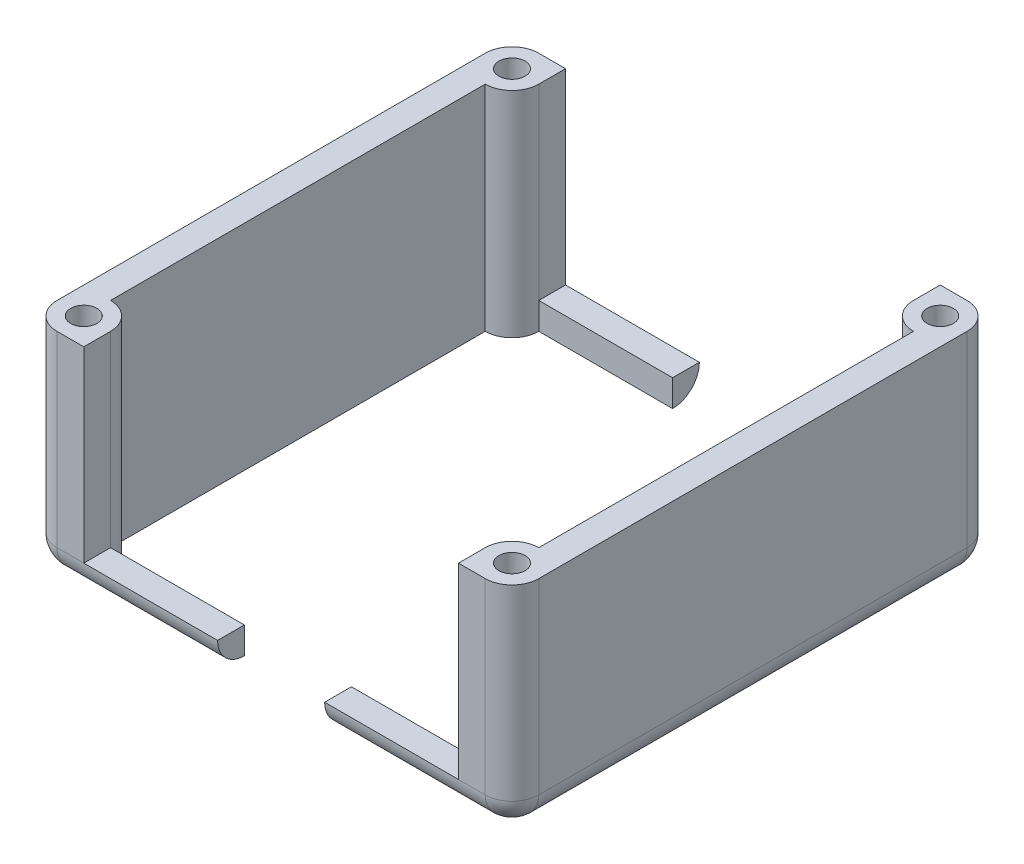
SolidWorks part; units mm, degrees
note: '?' marks a value the reader was unsure of. The reader was unsure of these and kept them because the rebuilt part matched: shared geometry of "Sketch5<3>", "Sketch13<4>", "Sketch13<5>", "Sketch13<6>", "Sketch24<4>".
ref_plane "Front Plane" through (0, 0, 0) normal (0, 0, 1) x (1, 0, 0)
ref_plane "Top Plane" through (0, 0, 0) normal (0, 1, 0) x (1, 0, 0)
ref_plane "Right Plane" through (0, 0, 0) normal (1, 0, 0) x (0, 0, -1)
sketch "Sketch1" plane through (0, 0, 0) normal (0, 1, 0) x (1, 0, 0)
  line L1 (-57.15, 57.15) -> (57.15, 57.15)
  line L2 (-57.15, 57.15) -> (-57.15, -57.15)
  line L3 (-57.15, -57.15) -> (57.15, -57.15)
  line L4 (57.15, 57.15) -> (57.15, -57.15)
  point P4 (0, 57.15)
  point P7 (-57.15, 0)
  dimension "D1" = 114.3
  dimension "D2" = 114.3
extrude "Boss-Extrude1" add sketch "Sketch1" along normal mid plane 50.8
sketch "Sketch2" plane through (0, 25.4, 0) normal (0, 1, 0) x (1, 0, 0)
  line L1 (-50.8, 50.8) -> (50.8, 50.8)
  line L2 (-50.8, 50.8) -> (-50.8, -50.8)
  line L3 (-50.8, -50.8) -> (50.8, -50.8)
  line L4 (50.8, 50.8) -> (50.8, -50.8)
  arc A0 (-50.8, 44.45) -> (-44.45, 50.8) centre (-50.8, 50.8) ccw
  arc A1 (44.45, 50.8) -> (50.8, 44.45) centre (50.8, 50.8) ccw
  arc A2 (-50.8, -44.45) -> (-44.45, -50.8) centre (-50.8, -50.8) cw
  arc A3 (44.45, -50.8) -> (50.8, -44.45) centre (50.8, -50.8) cw
  point P4 (0, 50.8)
  point P5 (50.8, 0)
  dimension "D3" = 6.35
  dimension "D4" = 6.35
  dimension "D5" = 6.35
  dimension "D6" = 6.35
  dimension "D1" = 101.6
  dimension "D2" = 101.6
extrude "Cut-Extrude1" cut sketch "Sketch2" against normal blind 50.8 contours L3 A3 L4 A1 L1 A0 L2 A2
hole_wizard "CBORE for #0 Binding Head Machine Screw1" positions "3DSketch2" profile "Sketch4" counterbore size "#0" standard "ANSI Inch"
sketch3d "3DSketch2"
  point P0 (-50.8, 25.4, -50.8)
  point P3 (50.8, 25.4, -50.8)
  point P6 (-50.8, 25.4, 50.8)
  point P9 (50.8, 25.4, 50.8)
sketch "Sketch4" plane through (-50.8, 25.4, -50.8) normal (1, 0, 0) x (0, 0, 1)
  line L0 (0, 0) -> (0, 18.288)
  line L1 (0, 18.288) -> (0.9271, 17.7309)
  line L2 (0.9271, 17.7309) -> (0.9271, 9.144)
  line L3 (0.9271, 9.144) -> (3.1115, 9.144)
  line L4 (3.1115, 9.144) -> (3.1115, 0)
  line L5 (3.1115, 0) -> (0, 0)
  line L10 (0, 18.288) -> (-0.9271, 17.7309) construction
  line L11 (0, -6.35) -> (0, 107.95) construction
  dimension "Hole Dia." = 1.8542
  dimension "Hole Depth" = 18.288
  dimension "C'Bore Dia." = 6.223
  dimension "C'Bore Depth" = 9.144
  dimension "Drill Angle" = 118
sketch "Sketch5" plane through (0, 0, -50.8) normal (0, 0, 1) x (1, 0, 0)
  line L0 (7.625, 3.175) -> (-7.625, 3.175) construction
  line L1 (-17.47, 20.645) -> (17.47, 20.645)
  line L2 (-17.47, 20.645) -> (-17.47, -14.295)
  line L3 (-17.47, -14.295) -> (17.47, -14.295)
  line L4 (17.47, 20.645) -> (17.47, -14.295)
  line L5 (-7.625, 10.8) -> (7.625, 10.8)
  line L6 (-7.625, 10.8) -> (-7.625, -4.45)
  line L7 (-7.625, -4.45) -> (7.625, -4.45)
  line L8 (7.625, 10.8) -> (7.625, -4.45)
  line L10 (-57.15, 25.4) -> (-57.15, -25.4) construction
  line L11 (0, 10.8) -> (0, -4.45) construction
  line L12 (-57.15, 25.4) -> (57.15, 25.4) construction
  point P8 (0, 10.8)
  point P9 (0, 20.645)
  point P12 (17.47, 3.175)
  point P13 (7.625, 3.175)
  dimension "D1" = 34.94
  dimension "D2" = 15.25
  dimension "D3" = 15.25
  dimension "D4" = 34.94
  dimension "D5" = 39.68
  dimension "D6" = 4.755
extrude "Cut-Extrude5" cut sketch "Sketch5" against normal blind 0.55
extrude "Cut-Extrude6" cut sketch "Sketch5<3>" against normal up to next
sketch "Sketch5<3>" plane through (0, 0, -50.8) normal (0, 0, 1) x (1, 0, 0) same geometry as "Sketch5"
sketch "Sketch13" plane through (0, 0, -57.15) normal (0, 0, -1) x (-1, 0, 0)
  line L0 (-57.15, 25.4) -> (57.15, 25.4) construction
  line L1 (-57.15, 25.4) -> (-57.15, -25.4) construction
  line L2 (57.15, 25.4) -> (57.15, -25.4) construction
  line L3 (-14.2875, -0.635) -> (-14.2875, -5.715) construction
  line L4 (14.2875, -5.715) -> (14.2875, -0.635) construction
  line L5 (13.7875, 0.602) -> (13.7875, -6.952)
  line L6 (14.7875, 0.602) -> (14.7875, -6.952)
  line L7 (11.5934, -5.8691) -> (16.9816, -0.4809)
  line L8 (11.5934, -0.4809) -> (16.9816, -5.8691)
  circle A0 centre (-14.2875, -3.175) radius 2.54
  circle A1 centre (14.2875, -3.175) radius 2.54
  circle A2 centre (14.2875, -3.175) radius 3.81
  point P19 (13.7875, -3.175)
  point P20 (14.7875, -3.175)
  dimension "D1" = 5.08
  dimension "D2" = 5.08
  dimension "D7" = 7.62
  dimension "D3" = 28.575
  dimension "D4" = 28.575
  dimension "D5" = 42.8625
  dimension "D6" = 42.8625
  dimension "D8" = 1
  dimension "D9" = 0.5
  dimension "D10" = 45
  dimension "D11" = 45
extrude "Boss-Extrude2" add sketch "Sketch13" along normal blind 1.27 contours A0
ref_plane "Plane1" through (14.2875, -3.175, -57.15) normal (0, -1, 0) x (-1, 0, 0)
sketch "Sketch14" plane through (14.2875, -3.175, -57.15) normal (0, -1, 0) x (-1, 0, 0)
  line L0 (0, 1.27) -> (0, 2.54)
  line L1 (2.54, 1.27) -> (-2.54, 1.27) construction
  line L2 (0, 2.54) -> (2.286, 2.54)
  line L3 (2.286, 2.54) -> (2.64, 1.651)
  line L4 (2.64, 1.651) -> (2.64, 1.27)
  line L5 (2.64, 1.27) -> (2.54, 1.27)
  line L6 (2.54, 0) -> (2.54, 1.27) construction
  line L7 (2.54, 1.27) -> (0, 1.27)
  dimension "D1" = 1.27
  dimension "D2" = 0.1
  dimension "D3" = 2.286
  dimension "D4" = 0.381
revolve "Revolve1" add sketch "Sketch14" angle 360 about L0
ref_plane "Plane2" through (-14.2875, -3.175, -57.15) normal (0, -1, 0) x (-1, 0, 0)
extrude "Cut-Extrude7" cut sketch "Sketch13<4>" against normal blind 2.54 contours L8 A1 L7 L6 | L6 A1 L8 | L5 A1 L6 L8 L7 | L7 A1 L6 | L6 A1 L5 L8 L7 | L7 L8 L6 | L8 L5 L7 | L8 A1 L7 L5 | L7 A1 L5 | L5 A1 L8
sketch "Sketch13<4>" plane through (0, 0, -57.15) normal (0, 0, -1) x (-1, 0, 0) same geometry as "Sketch13"
extrude "Cut-Extrude8" cut sketch "Sketch13<5>" against normal blind 0.635 contours L7 A2 L5 A1 | L6 A2 L8 A1 | L7 A2 L6 A1 | L5 A2 L8 A1
sketch "Sketch13<5>" plane through (0, 0, -57.15) normal (0, 0, -1) x (-1, 0, 0) same geometry as "Sketch13"
extrude "Cut-Extrude9" cut sketch "Sketch13<6>" against normal blind 1.27 contours L6 A2 L5 A1 | L5 A2 L6 A1
sketch "Sketch13<6>" plane through (0, 0, -57.15) normal (0, 0, -1) x (-1, 0, 0) same geometry as "Sketch13"
sketch "Sketch17" plane through (-14.2875, -3.175, -57.15) normal (0, -1, 0) x (-1, 0, 0)
  line L0 (0, -1.27) -> (0, -2.54)
  line L1 (0.5, -1.27) -> (-0.5, -1.27) construction
  line L2 (0, -2.54) -> (2.286, -2.54)
  line L3 (2.286, -2.54) -> (2.64, -1.651)
  line L7 (2.54, -1.27) -> (0, -1.27)
  line L8 (2.64, -1.651) -> (2.64, -1.27)
  line L9 (2.64, -1.27) -> (2.54, -1.27)
  dimension "D1" = 2.54
  dimension "D2" = 2.286
  dimension "D3" = 0.1
  dimension "D4" = 1.27
  dimension "D5" = 0.381
revolve "Cut-Revolve1" cut sketch "Sketch17" angle 360 about L0
ref_plane "Plane3" through (0, 3.175, 0) normal (0, -1, 0) x (0, 0, 1)
ref_axis "Axis1" through (0, 3.175, 62.865) along (0, 0, -1)?
ref_axis "Axis2" through (0, 59.3725, 0) along (0, -1, 0)
sketch "Sketch20" plane through (0, 0, -57.15) normal (0, 0, -1) x (-1, 0, 0)
  line L1 (-13.97, 17.145) -> (13.97, 17.145)
  line L2 (-13.97, 17.145) -> (-13.97, -10.795)
  line L3 (-13.97, -10.795) -> (13.97, -10.795)
  line L4 (13.97, 17.145) -> (13.97, -10.795)
  point P4 (0, 17.145)
  point P9 (13.97, 3.175)
  dimension "D1" = 27.94
  dimension "D2" = 27.94
hole_wizard "CBORE for M5 Hex Head Bolt2" positions "3DSketch4" profile "Sketch21" counterbore size "M5" standard "ANSI Metric"
sketch3d "3DSketch4"
  point P0 (13.97, 17.145, -57.15)
  point P3 (-13.97, 17.145, -57.15)
  point P6 (-13.97, -10.795, -57.15)
  point P9 (13.97, -10.795, -57.15)
sketch "Sketch21" plane through (13.97, 17.145, -57.15) normal (1, 0, 0) x (0, 1, 0)
  line L0 (0, 0) -> (0, 18.288)
  line L1 (0, 18.288) -> (2.75, 16.6356)
  line L2 (2.75, 16.6356) -> (2.75, 5.8)
  line L3 (2.75, 5.8) -> (2.25, 5.8)
  line L4 (2.25, 5.8) -> (2.25, 0)
  line L5 (2.25, 0) -> (0, 0)
  line L10 (0, 18.288) -> (-2.75, 16.6356) construction
  line L11 (0, -6.35) -> (0, 107.95) construction
  dimension "Hole Dia." = 5.5
  dimension "Hole Depth" = 18.288
  dimension "C'Bore Dia." = 4.5
  dimension "C'Bore Depth" = 5.8
  dimension "Drill Angle" = 118
sketch "Sketch23" plane through (0, 0, -59.69) normal (0, 0, -1) x (-1, 0, 0)
  line L0 (-14.7875, -0.5828) -> (-14.7875, -5.7672)
  line L1 (-13.7875, -0.5828) -> (-13.7875, -5.7672)
  line L2 (-14.2875, -0.535) -> (-14.2875, -5.815) construction
  circle A0 centre (-14.2875, -3.175) radius 2.64 construction
  circle A1 centre (-14.2875, -3.175) radius 2.64
  circle M1 centre (-14.2875, -3.175) radius 2.286
  dimension "D1" = 5.28
  dimension "D2" = 0.5
  dimension "D3" = 0.5
extrude "Cut-Extrude10" cut sketch "Sketch23" against normal blind 2.032 contours L2 L0 M1 | L2 L1 M1 | L2 A1 L0 M1 | A1 L2 L1 M1 | L2 A1 L1 M1 | L2 L0 A1 M1
pattern_circular "CirPattern1" count 4 every 90 about axis through (0, 3.175, 0) along (0, 0, 1) of "Boss-Extrude2", "Revolve1", "Cut-Extrude7", "Cut-Extrude8", "Cut-Extrude9", "Cut-Revolve1", "Cut-Extrude10"
ref_plane "Plane4" through (0, 3.175, 0) normal (0, -1, 0) x (-1, 0, 0)
ref_axis "Axis3" through (-62.865, 3.175, 0) along (1, 0, 0)
pattern_circular "CirPattern2" count 2 over 180 about axis through (0, 3.175, 0) along (1, 0, 0) of "CirPattern1", "Boss-Extrude2", "Revolve1", "Cut-Extrude7", "Cut-Extrude8", "Cut-Extrude9", "Cut-Revolve1", "Cut-Extrude10"
pattern_circular "CirPattern3" count 2 over 180 about axis through (0, 3.175, 0) along (1, 0, 0) of "Cut-Extrude5", "Cut-Extrude6", "CBORE for M5 Hex Head Bolt2"
fillet "Fillet1" radius 6.35 8 edges at (0, -25.4, -57.15) (57.15, -25.4, 0) (0, -25.4, 57.15) (-57.15, -25.4, 0) (-57.15, 0, 57.15) (-57.15, 0, -57.15) (57.15, 0, 57.15) (57.15, 0, -57.15)
sketch "Sketch24" plane through (0, 0, -50.8) normal (0, 0, 1) x (1, 0, 0)
  line L0 (44.45, -25.4) -> (44.45, 25.4) construction
  line L1 (-44.45, 25.4) -> (44.45, 25.4)
  line L2 (-44.45, 25.4) -> (-44.45, -19.05)
  line L3 (-44.45, -19.05) -> (44.45, -19.05)
  line L4 (44.45, 25.4) -> (44.45, -19.05)
  line L5 (-44.45, -25.4) -> (44.45, -25.4) construction
  line L6 (-6.35, -19.05) -> (6.35, -19.05)
  line L7 (-6.35, -19.05) -> (-6.35, -25.4)
  line L8 (-6.35, -25.4) -> (6.35, -25.4)
  line L9 (6.35, -19.05) -> (6.35, -25.4)
  line L10 (0, 59.3725) -> (0, -59.3725) construction
  line L11 (6.35, -19.05) -> (12.7, -19.05)
  line L12 (6.35, -19.05) -> (6.35, -25.4)
  line L13 (6.35, -25.4) -> (12.7, -25.4)
  line L14 (12.7, -19.05) -> (12.7, -25.4)
  line L15 (-12.7, -19.05) -> (-6.35, -19.05)
  line L16 (-12.7, -19.05) -> (-12.7, -25.4)
  line L17 (-12.7, -25.4) -> (-6.35, -25.4)
  line L18 (-6.35, -19.05) -> (-6.35, -25.4)
  point P21 (-6.35, -22.225)
  point P22 (0, -25.4)
  point P25 (12.7, -22.225)
  dimension "D1" = 6.35
  dimension "D2" = 6.35
  dimension "D3" = 12.7
  dimension "D4" = 6.35
  dimension "D5" = 38.1
  dimension "D6" = 38.1
extrude "Cut-Extrude12" cut sketch "Sketch24" against normal up to next contours L3 L4 L1 L2 | L8 L9 L6 L7
extrude "Cut-Extrude13" cut sketch "Sketch24<4>" against normal up to next contours L14 L13 L12 L11 | L16 L17 L18 L15
sketch "Sketch24<4>" plane through (0, 0, -50.8) normal (0, 0, 1) x (1, 0, 0) same geometry as "Sketch24"
pattern_circular "CirPattern4" count 2 over 180 about axis through (0, -19.05, 0) along (0, 0, 1) of "Cut-Extrude12"
sketch "Sketch25" plane through (0, 0, 50.8) normal (0, 0, -1) x (-1, 0, 0)
  line L1 (-12.7, -19.05) -> (12.7, -19.05)
  line L2 (-12.7, -19.05) -> (-12.7, -25.4)
  line L3 (-12.7, -25.4) -> (12.7, -25.4)
  line L4 (12.7, -19.05) -> (12.7, -25.4)
extrude "Cut-Extrude14" cut sketch "Sketch25" against normal up to next
